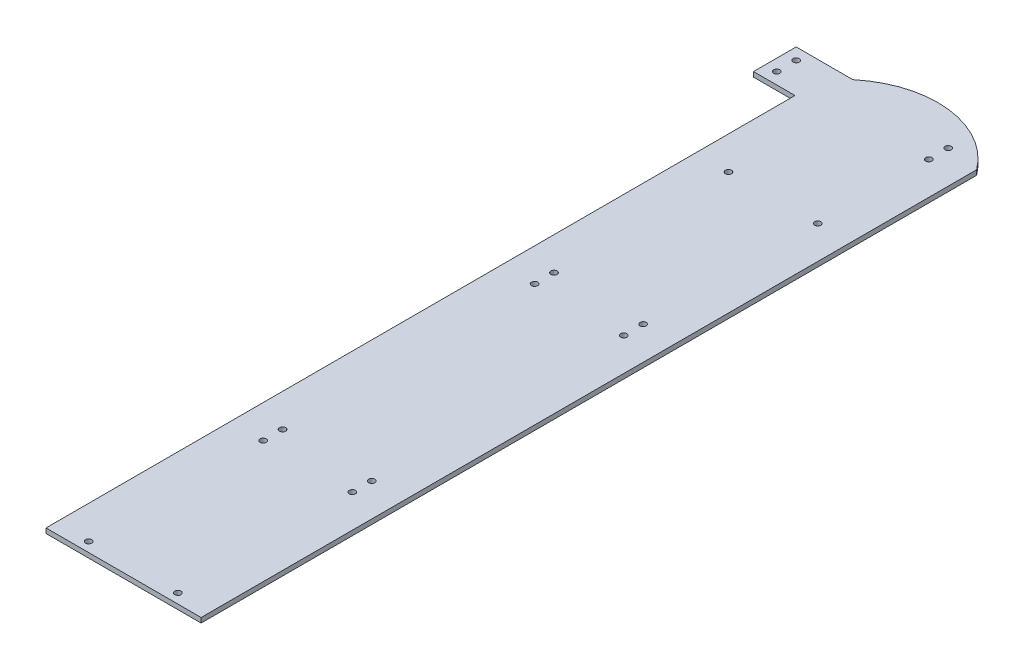
SolidWorks part; units mm, degrees
ref_plane "Front Plane" through (0, 0, 0) normal (0, 0, 1) x (1, 0, 0)
ref_plane "Top Plane" through (0, 0, 0) normal (0, 1, 0) x (1, 0, 0)
ref_plane "Right Plane" through (0, 0, 0) normal (1, 0, 0) x (0, 0, -1)
sketch "Sketch1" plane through (0, 0, 0) normal (0, 1, 0) x (1, 0, 0)
  line L2 (0, 0) -> (0, -508)
  line L3 (0, -508) -> (101.6, -508)
  line L4 (101.6, 0) -> (101.6, -508)
  arc A0 (0, 0) -> (101.6, 0) centre (50.8, -38.1) cw
  dimension "D3" = 63.5
  dimension "D1" = 508
  dimension "D2" = 101.6
extrude "Boss-Extrude1" add sketch "Sketch1" along normal blind 3.175
sketch "Sketch2" plane through (0, 0, 0) normal (0, -1, 0) x (1, 0, 0)
  line L0 (21.59, 82.55) -> (80.01, 82.55) construction
  line L1 (0, 508) -> (101.6, 508) construction
  circle A0 centre (21.59, 501.65) radius 2.032
  circle A1 centre (80.01, 501.65) radius 2.032
  circle A2 centre (21.59, 82.55) radius 2.032
  circle A3 centre (80.01, 82.55) radius 2.032
  arc A4 (0, 0) -> (101.6, 0) centre (50.8, 38.1) ccw construction
  circle A5 centre (21.59, 209.55) radius 2.032
  circle A6 centre (80.01, 209.55) radius 2.032
  circle A7 centre (21.59, 196.85) radius 2.032
  circle A8 centre (80.01, 196.85) radius 2.032
  circle A9 centre (21.59, 374.65) radius 2.032
  circle A10 centre (80.01, 374.65) radius 2.032
  circle A11 centre (21.59, 387.35) radius 2.032
  circle A12 centre (80.01, 387.35) radius 2.032
  point P11 (50.8, -25.4)
  point P12 (50.8, 82.55)
  dimension "D1" = 4.064
  dimension "D2" = 58.42
  dimension "D3" = 6.35
  dimension "D4" = 419.1
  dimension "D5" = 114.3
  dimension "D6" = 177.8
  dimension "D7" = 12.7
  dimension "D8" = 12.7
extrude "Cut-Extrude1" cut sketch "Sketch2" against normal through all
sketch "Sketch3" plane through (0, 3.175, 0) normal (0, 1, 0) x (1, 0, 0)
  line L0 (0, 0) -> (0, -508) construction
  line L1 (-30.48, 10.541) -> (20.32, 10.541)
  line L2 (-30.48, 10.541) -> (-30.48, -22.2585)
  line L3 (-30.48, -22.2585) -> (20.32, -22.2585)
  line L4 (20.32, 10.541) -> (20.32, -22.2585)
  point P4 (-23.821, 4.3863)
  point P5 (-23.4173, 8.2215)
  dimension "D1" = 32.7995
  dimension "D2" = 50.8
  dimension "D3" = 30.48
  dimension "D4" = 22.2585
extrude "Boss-Extrude4" add sketch "Sketch3" against normal up to surface (3.175 mm away) up to face at (80.01, 0, 207.518)
sketch "Sketch6" plane through (0, 3.175, 0) normal (0, 1, 0) x (1, 0, 0)
  line L0 (101.6, -508) -> (101.6, 0) construction
  line L1 (0, -508) -> (101.6, -508) construction
  circle A0 centre (-19.558, 2.921) radius 2.032
  circle A1 centre (-19.558, -9.779) radius 2.032
  circle A2 centre (80.01, 2.921) radius 2.032
  circle A3 centre (80.01, -9.779) radius 2.032
  point P8 (0, 0)
  dimension "D1" = 4.064
  dimension "D2" = 21.59
  dimension "D3" = 99.568
  dimension "D4" = 12.7
  dimension "D5" = 498.221
extrude "Cut-Extrude4" cut sketch "Sketch6" against normal through all
sketch "Sketch7" plane through (0, 3.175, 0) normal (0, 1, 0) x (1, 0, 0)
  line L0 (-30.48, 10.541) -> (-30.48, -22.2585) construction
  line L1 (0, -22.2585) -> (-30.48, -22.2585)
  line L2 (0, -22.2585) -> (0, -17.399)
  line L3 (0, -17.399) -> (-30.48, -17.399)
  line L4 (-30.48, -22.2585) -> (-30.48, -17.399)
  line L6 (-30.48, 10.541) -> (-27.178, 10.541)
  line L7 (-30.48, 10.541) -> (-30.48, -17.399)
  line L8 (-30.48, -17.399) -> (-27.178, -17.399)
  line L9 (-27.178, 10.541) -> (-27.178, -17.399)
  line M8 (9.9797, 10.541) -> (-30.48, 10.541)
  line M9 (-30.48, 10.541) -> (-30.48, -22.2585)
  line M10 (-30.48, -22.2585) -> (0, -22.2585)
  dimension "D1" = 4.8595
  dimension "D2" = 3.302
extrude "Cut-Extrude5" cut sketch "Sketch7" against normal through all contours L2 L3 M9 M10 | L9 L3 M8 M9 region at (-15.24, 3.175, 19.8288) region at (-28.829, 3.175, 3.429)
